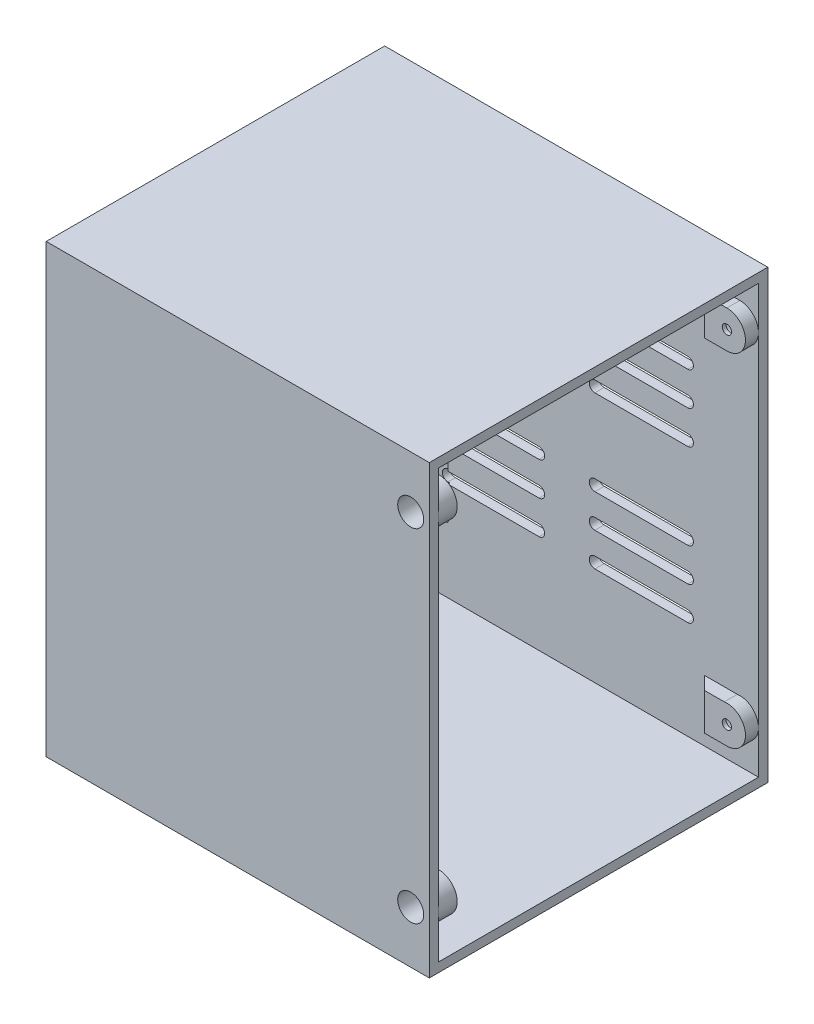
SolidWorks part; units mm, degrees
ref_plane "Front Plane" through (0, 0, 0) normal (0, 0, 1) x (1, 0, 0)
ref_plane "Top Plane" through (0, 0, 0) normal (0, 1, 0) x (1, 0, 0)
ref_plane "Right Plane" through (0, 0, 0) normal (1, 0, 0) x (0, 0, -1)
sketch "Sketch1" plane through (205.5525, 0, 0) normal (1, 0, 0) x (0, 0, -1)
  line L0 (1.5129, 48.8646) -> (1.513, -71.1354) construction
  line L1 (-89.4871, 48.8644) -> (1.5129, 48.8646) construction
  line L2 (-89.4871, 48.8644) -> (-89.487, -71.1356) construction
  line L3 (-89.487, -71.1356) -> (1.513, -71.1354) construction
  line L4 (1.5129, 48.8646) -> (1.513, -71.1354)
  line L5 (-89.4871, 48.8644) -> (1.5129, 48.8646)
  line L6 (-89.4871, 48.8644) -> (-89.487, -71.1356)
  line L7 (-89.487, -71.1356) -> (1.513, -71.1354)
  line L8 (-86.987, -68.6356) -> (-0.987, -68.6355)
  line L9 (-0.9871, 46.3645) -> (-0.987, -68.6355)
  line L10 (-86.9871, 46.3644) -> (-0.9871, 46.3645)
  line L11 (-86.9871, 46.3644) -> (-86.987, -68.6356)
  dimension "D1" = 2.5
extrude "Boss-Extrude1" add sketch "Sketch1" along normal up to surface (103 mm away)
sketch "Sketch2" plane through (0, 0, 86.9871) normal (0, 0, -1) x (-1, 0, 0)
  line L0 (-205.5525, 46.3645) -> (-205.5525, -68.6355) construction
  line L1 (-208.4525, -46.1353) -> (-206.5525, -46.1353)
  line L2 (-208.4525, -46.1353) -> (-208.4525, -40.1355)
  line L3 (-208.4525, -40.1355) -> (-206.5525, -40.1355)
  line L4 (-206.5525, -46.1353) -> (-206.5525, -40.1355)
  line L5 (-206.5525, 23.8645) -> (-208.4525, 23.8645)
  line L6 (-206.5525, 23.8645) -> (-206.5525, 17.8647)
  line L7 (-206.5525, 17.8647) -> (-208.4525, 17.8647)
  line L8 (-208.4525, 23.8645) -> (-208.4525, 17.8647)
  dimension "D1" = 0.1
  dimension "D2" = 1
  dimension "D3" = 0.1
  dimension "D4" = 1
  dimension "D5" = 0
  dimension "D6" = 0
  dimension "D7" = 0
  dimension "D8" = 0
extrude "Boss-Extrude2" add sketch "Sketch2" along normal offset from surface (1.3 mm away) 0.2
sketch "Sketch3" plane through (0, 0, 0.9871) normal (0, 0, 1) x (1, 0, 0)
  line L1 (210.0525, 28.8645) -> (225.0525, 28.8645)
  line L2 (210.0525, 28.8645) -> (210.0525, -51.1355)
  line L3 (210.0525, -51.1355) -> (225.0525, -51.1355)
  line L4 (225.0525, 28.8645) -> (225.0525, -51.1355)
  line L6 (205.5525, -68.6355) -> (205.5525, 46.3645) construction
  line L7 (308.5525, -71.1355) -> (205.5525, -71.1355) construction
  line L8 (308.5525, 48.8645) -> (205.5525, 48.8645) construction
  dimension "D1" = 4.5
  dimension "D2" = 15
  dimension "D3" = 20
  dimension "D4" = 20
extrude "Cut-Extrude1" cut sketch "Sketch3" against normal blind 0.5
sketch "Sketch4" plane through (0, 0, 0.9871) normal (0, 0, 1) x (1, 0, 0)
  line L0 (211.5525, 39.8645) -> (205.5525, 39.8645)
  line L1 (205.5525, -68.6355) -> (205.5525, 46.3645) construction
  line L2 (211.5525, 29.8645) -> (205.5525, 29.8645)
  line L3 (205.5525, 29.8645) -> (205.5525, 39.8645)
  line L4 (211.5525, -52.1355) -> (205.5525, -52.1355)
  line L5 (211.5525, -62.1355) -> (205.5525, -62.1355)
  line L6 (205.5525, -62.1355) -> (205.5525, -52.1355)
  line L7 (303.5525, -62.1355) -> (293.5525, -62.1355)
  line L8 (293.5525, -62.1355) -> (293.5525, -52.1855)
  line L9 (303.6025, -52.1855) -> (293.5525, -52.1855)
  line L10 (303.5525, 29.8645) -> (293.5525, 29.8645)
  line L11 (303.5525, 39.8645) -> (293.5525, 39.8645)
  line L12 (293.5525, 39.8645) -> (293.5525, 29.8645)
  circle A0 centre (211.5525, 34.8645) radius 2.25 construction
  circle A1 centre (211.5525, -57.1355) radius 2.25 construction
  circle A2 centre (211.5525, 34.8645) radius 2.25 construction
  circle A3 centre (211.5525, -57.1355) radius 2.25 construction
  circle A4 centre (211.5525, -57.1355) radius 5
  circle A5 centre (211.5525, 34.8645) radius 5
  circle A6 centre (211.5525, -57.1355) radius 3.5
  circle A7 centre (211.5525, 34.8645) radius 3.5
  circle A8 centre (211.5525, 34.8645) radius 1.25
  circle A9 centre (211.5525, -57.1355) radius 1.25
  circle A10 centre (303.5525, 34.8645) radius 1.6 construction
  circle A11 centre (303.5525, -57.1355) radius 1.6 construction
  circle A12 centre (303.5525, 34.8645) radius 1.6 construction
  circle A13 centre (303.5525, -57.1355) radius 1.6 construction
  circle A14 centre (303.5525, 34.8645) radius 5
  circle A15 centre (303.5525, -57.1355) radius 5
  circle A16 centre (303.5525, -57.1355) radius 3.5
  circle A17 centre (303.5525, -57.1355) radius 1.25
  circle A18 centre (303.5525, 34.8645) radius 3.5
  circle A19 centre (303.5525, 34.8645) radius 1.25
  line M7 (205.5525, 46.3645) -> (205.5525, -68.6355)
  dimension "D1" = 10
  dimension "D2" = 10
  dimension "D3" = 7
  dimension "D4" = 7
  dimension "D5" = 2.5
  dimension "D6" = 2.5
  dimension "D7" = 10
  dimension "D8" = 7
  dimension "D9" = 2.5
  dimension "D10" = 10
  dimension "D11" = 7
  dimension "D12" = 2.5
  dimension "D13" = 10
  dimension "D14" = 10
extrude "Boss-Extrude3" add sketch "Sketch4" along normal up to surface (3.5 mm away) contours A5 A7 | A4 A6 | A5 L0 L2 M7 | A4 L4 L5 M7 | A15 A16 | A14 A18 | A14 L11 L12 L10 | A15 L9 L8 L7 region at (206.4359, 34.8645, 0.9871) region at (208.5525, -52.2521, 0.9871) region at (214.988, 38.3001, 0.9871) region at (214.988, -53.6999, 0.9871) region at (298.7061, -57.479, 0.9871) region at (296.6787, -57.1748, 0.9871) region at (296.6915, 34.8645, 0.9871) region at (298.6939, 34.8645, 0.9871)
extrude "Boss-Extrude4" add sketch "Sketch4<3>" against normal blind 1 from surface contours A7 A8 | A18 A19 | A16 A17 | A6 A9 region at (208.1515, -57.1355, 0.9871) region at (208.1515, 34.8645, 0.9871) region at (300.1515, -57.1355, 0.9871) region at (300.1515, 34.8645, 0.9871) starting at face at (307.0525, 34.8645, 4.4871)
sketch "Sketch4<3>" plane through (0, 0, 0.9871) normal (0, 0, 1) x (1, 0, 0) same geometry as "Sketch4"
extrude "Cut-Extrude2" cut sketch "Sketch4<4>" against normal through all contours A6 A9 | A9 | A7 A8 | A8 | A17 | A16 A17 | A19 | A18 A19 region at (208.1515, -57.1355, 0.9871) region at (208.1515, 34.8645, 0.9871) region at (211.5525, 34.8645, 0.9871) region at (211.5525, -57.1355, 0.9871) region at (300.1515, -57.1355, 0.9871) region at (303.5525, -57.1355, 0.9871) region at (300.1515, 34.8645, 0.9871) region at (303.5525, 34.8645, 0.9871)
sketch "Sketch4<4>" plane through (0, 0, 0.9871) normal (0, 0, 1) x (1, 0, 0) same geometry as "Sketch4"
chamfer "Chamfer1" distance 4 angle 45 1 edges at (293.5525, -57.1605, 4.4871)
chamfer "Chamfer2" distance 4 angle 45 1 edges at (293.5525, 34.8645, 4.4871)
sketch "Sketch5" plane through (0, 0, -1.5129) normal (0, 0, -1) x (-1, 0, 0)
  line L0 (-257.0525, 48.8645) -> (-257.0525, -71.1355) construction
  line L1 (-308.5525, 48.8645) -> (-205.5525, 48.8645) construction
  line L2 (-308.5525, -71.1355) -> (-205.5525, -71.1355) construction
  line L3 (-308.5525, -11.1355) -> (-205.5525, -11.1355) construction
  line L4 (-308.5525, -71.1355) -> (-308.5525, 48.8645) construction
  line L5 (-205.5525, 48.8645) -> (-205.5525, -71.1355) construction
  line L6 (-289.5525, 10.8645) -> (-289.5525, 7.8645)
  line L7 (-289.5525, 1.8645) -> (-264.5525, 1.8645)
  line L8 (-289.5525, 1.8645) -> (-289.5525, -1.1355)
  line L9 (-289.5525, -1.1355) -> (-264.5525, -1.1355)
  line L10 (-264.5525, 1.8645) -> (-264.5525, -1.1355)
  line L11 (-289.5525, 10.8645) -> (-264.5525, 10.8645)
  line L12 (-264.5525, 10.8645) -> (-264.5525, 7.8645)
  line L13 (-289.5525, 7.8645) -> (-264.5525, 7.8645)
  line L14 (-289.5525, 19.8645) -> (-289.5525, 16.8645)
  line L15 (-289.5525, 19.8645) -> (-264.5525, 19.8645)
  line L16 (-264.5525, 19.8645) -> (-264.5525, 16.8645)
  line L17 (-289.5525, 16.8645) -> (-264.5525, 16.8645)
  line L18 (-224.5525, 16.8645) -> (-249.5525, 16.8645)
  line L19 (-249.5525, 19.8645) -> (-249.5525, 16.8645)
  line L20 (-224.5525, 19.8645) -> (-249.5525, 19.8645)
  line L21 (-224.5525, 19.8645) -> (-224.5525, 16.8645)
  line L22 (-224.5525, 7.8645) -> (-249.5525, 7.8645)
  line L23 (-249.5525, 10.8645) -> (-249.5525, 7.8645)
  line L24 (-224.5525, 10.8645) -> (-249.5525, 10.8645)
  line L25 (-249.5525, 1.8645) -> (-249.5525, -1.1355)
  line L26 (-224.5525, -1.1355) -> (-249.5525, -1.1355)
  line L27 (-224.5525, 1.8645) -> (-224.5525, -1.1355)
  line L28 (-224.5525, 1.8645) -> (-249.5525, 1.8645)
  line L29 (-224.5525, 10.8645) -> (-224.5525, 7.8645)
  line L30 (-224.5525, -33.1355) -> (-224.5525, -30.1355)
  line L31 (-224.5525, -24.1355) -> (-249.5525, -24.1355)
  line L32 (-224.5525, -24.1355) -> (-224.5525, -21.1355)
  line L33 (-224.5525, -21.1355) -> (-249.5525, -21.1355)
  line L34 (-249.5525, -24.1355) -> (-249.5525, -21.1355)
  line L35 (-224.5525, -33.1355) -> (-249.5525, -33.1355)
  line L36 (-249.5525, -33.1355) -> (-249.5525, -30.1355)
  line L37 (-224.5525, -30.1355) -> (-249.5525, -30.1355)
  line L38 (-224.5525, -42.1355) -> (-224.5525, -39.1355)
  line L39 (-224.5525, -42.1355) -> (-249.5525, -42.1355)
  line L40 (-249.5525, -42.1355) -> (-249.5525, -39.1355)
  line L41 (-224.5525, -39.1355) -> (-249.5525, -39.1355)
  line L42 (-289.5525, -39.1355) -> (-264.5525, -39.1355)
  line L43 (-264.5525, -42.1355) -> (-264.5525, -39.1355)
  line L44 (-289.5525, -42.1355) -> (-264.5525, -42.1355)
  line L45 (-289.5525, -42.1355) -> (-289.5525, -39.1355)
  line L46 (-289.5525, -30.1355) -> (-264.5525, -30.1355)
  line L47 (-264.5525, -33.1355) -> (-264.5525, -30.1355)
  line L48 (-289.5525, -33.1355) -> (-264.5525, -33.1355)
  line L49 (-264.5525, -24.1355) -> (-264.5525, -21.1355)
  line L50 (-289.5525, -21.1355) -> (-264.5525, -21.1355)
  line L51 (-289.5525, -24.1355) -> (-289.5525, -21.1355)
  line L52 (-289.5525, -24.1355) -> (-264.5525, -24.1355)
  line L53 (-289.5525, -33.1355) -> (-289.5525, -30.1355)
  arc A0 (-264.5525, 1.8645) -> (-264.5525, -1.1355) centre (-264.5525, 0.3645) cw
  arc A1 (-289.5525, -1.1355) -> (-289.5525, 1.8645) centre (-289.5525, 0.3645) cw
  arc A2 (-264.5525, 10.8645) -> (-264.5525, 7.8645) centre (-264.5525, 9.3645) cw
  arc A3 (-289.5525, 7.8645) -> (-289.5525, 10.8645) centre (-289.5525, 9.3645) cw
  arc A4 (-264.5525, 19.8645) -> (-264.5525, 16.8645) centre (-264.5525, 18.3645) cw
  arc A5 (-289.5525, 16.8645) -> (-289.5525, 19.8645) centre (-289.5525, 18.3645) cw
  arc A6 (-224.5525, 16.8645) -> (-224.5525, 19.8645) centre (-224.5525, 18.3645) ccw
  arc A7 (-249.5525, 19.8645) -> (-249.5525, 16.8645) centre (-249.5525, 18.3645) ccw
  arc A8 (-224.5525, 7.8645) -> (-224.5525, 10.8645) centre (-224.5525, 9.3645) ccw
  arc A9 (-249.5525, 10.8645) -> (-249.5525, 7.8645) centre (-249.5525, 9.3645) ccw
  arc A10 (-224.5525, -1.1355) -> (-224.5525, 1.8645) centre (-224.5525, 0.3645) ccw
  arc A11 (-249.5525, 1.8645) -> (-249.5525, -1.1355) centre (-249.5525, 0.3645) ccw
  arc A12 (-249.5525, -24.1355) -> (-249.5525, -21.1355) centre (-249.5525, -22.6355) cw
  arc A13 (-224.5525, -21.1355) -> (-224.5525, -24.1355) centre (-224.5525, -22.6355) cw
  arc A14 (-249.5525, -33.1355) -> (-249.5525, -30.1355) centre (-249.5525, -31.6355) cw
  arc A15 (-224.5525, -30.1355) -> (-224.5525, -33.1355) centre (-224.5525, -31.6355) cw
  arc A16 (-249.5525, -42.1355) -> (-249.5525, -39.1355) centre (-249.5525, -40.6355) cw
  arc A17 (-224.5525, -39.1355) -> (-224.5525, -42.1355) centre (-224.5525, -40.6355) cw
  arc A18 (-289.5525, -39.1355) -> (-289.5525, -42.1355) centre (-289.5525, -40.6355) ccw
  arc A19 (-264.5525, -42.1355) -> (-264.5525, -39.1355) centre (-264.5525, -40.6355) ccw
  arc A20 (-289.5525, -30.1355) -> (-289.5525, -33.1355) centre (-289.5525, -31.6355) ccw
  arc A21 (-264.5525, -33.1355) -> (-264.5525, -30.1355) centre (-264.5525, -31.6355) ccw
  arc A22 (-289.5525, -21.1355) -> (-289.5525, -24.1355) centre (-289.5525, -22.6355) ccw
  arc A23 (-264.5525, -24.1355) -> (-264.5525, -21.1355) centre (-264.5525, -22.6355) ccw
  dimension "D1" = 3
  dimension "D2" = 25
  dimension "D3" = 10
  dimension "D4" = 7.5
  dimension "D6" = 6
  dimension "D5" = 3
extrude "Cut-Extrude3" cut sketch "Sketch5" against normal blind 3 contours L14 L17 L16 L15 | A5 L14 | A4 L16 | A1 L8 | L10 L7 L8 L9 | A0 L10 | A2 L12 | L6 L13 L12 L11 | A3 L6 | A17 L38 | L38 L41 L40 L39 | A16 L40 | A14 L36 | L30 L37 L36 L35 | A15 L30 | A13 L32 | L34 L31 L32 L33 | A12 L34 | L51 A22 | L51 L52 L49 L50 | L49 A23 | L47 A21 | L53 L48 L47 L46 | L53 A20 | L45 A18 | L45 L44 L43 L42 | L43 A19 | L21 A6 | L21 L20 L19 L18 | L19 A7 | L23 A9 | L29 L24 L23 L22 | L29 A8 | L27 A10 | L27 L28 L25 L26 | L25 A11 region at (277.0525, 9.3645, -1.5129) region at (290.1891, 9.3645, -1.5129) region at (263.9159, 9.3645, -1.5129) region at (277.0525, 0.3645, -1.5129) region at (290.1891, 0.3645, -1.5129) region at (263.9159, 0.3645, -1.5129) region at (277.0525, 18.3645, -1.5129) region at (290.1891, 18.3645, -1.5129) region at (263.9159, 18.3645, -1.5129) region at (237.0525, 18.3645, -1.5129) region at (223.9159, 18.3645, -1.5129) region at (250.1891, 18.3645, -1.5129) region at (237.0525, 9.3645, -1.5129) region at (223.9159, 9.3645, -1.5129) region at (250.1891, 9.3645, -1.5129) region at (237.0525, 0.3645, -1.5129) region at (250.1891, 0.3645, -1.5129) region at (223.9159, 0.3645, -1.5129) region at (237.0525, -31.6355, -1.5129) region at (223.9159, -31.6355, -1.5129) region at (250.1891, -31.6355, -1.5129) region at (237.0525, -22.6355, -1.5129) region at (223.9159, -22.6355, -1.5129) region at (250.1891, -22.6355, -1.5129) region at (237.0525, -40.6355, -1.5129) region at (223.9159, -40.6355, -1.5129) region at (250.1891, -40.6355, -1.5129) region at (277.0525, -40.6355, -1.5129) region at (290.1891, -40.6355, -1.5129) region at (263.9159, -40.6355, -1.5129) region at (277.0525, -31.6355, -1.5129) region at (290.1891, -31.6355, -1.5129) region at (263.9159, -31.6355, -1.5129) region at (277.0525, -22.6355, -1.5129) region at (263.9159, -22.6355, -1.5129) region at (290.1891, -22.6355, -1.5129)
extrude "Boss-Extrude5" add sketch "Sketch4<6>" against normal up to surface (5 mm away) from surface contours A15 L9 L8 L7 | A15 A16 | A14 L11 L12 L10 | A14 A18 region at (298.7061, -57.479, 0.9871) region at (296.6787, -57.1748, 0.9871) region at (296.6915, 34.8645, 0.9871) region at (298.6939, 34.8645, 0.9871) starting at face at (257.0525, -11.1355, 86.9871)
sketch "Sketch4<6>" plane through (0, 0, 0.9871) normal (0, 0, 1) x (1, 0, 0) same geometry as "Sketch4"
extrude "Boss-Extrude6" add sketch "Sketch4<7>" along normal blind 1 from surface contours A14 A18 | A18 A19 | A16 A17 | A15 A16 region at (298.7061, -57.479, 0.9871) region at (298.6939, 34.8645, 0.9871) region at (300.1515, -57.1355, 0.9871) region at (300.1515, 34.8645, 0.9871) starting at face at (299.8025, 34.8645, 81.9871)
sketch "Sketch4<7>" plane through (0, 0, 0.9871) normal (0, 0, 1) x (1, 0, 0) same geometry as "Sketch4"
extrude "Cut-Extrude4" cut sketch "Sketch4<8>" along normal through all from surface contours A16 A17 | A18 A19 | A17 | A19 region at (300.1515, -57.1355, 0.9871) region at (303.5525, -57.1355, 0.9871) region at (300.1515, 34.8645, 0.9871) region at (303.5525, 34.8645, 0.9871) starting at face at (207.5025, 20.8646, 86.9871)
sketch "Sketch4<8>" plane through (0, 0, 0.9871) normal (0, 0, 1) x (1, 0, 0) same geometry as "Sketch4"
chamfer "Chamfer3" distance 5 angle 45 1 edges at (293.5525, -57.1605, 81.9871)
chamfer "Chamfer4" distance 5 angle 45 1 edges at (293.5525, 34.8645, 81.9871)
equation "\"R\"=9.03994"
equation "\"R_MOUNT_OUTER\"=10"
equation "\"D1@Sketch4\"=\"R_MOUNT_OUTER\""
equation "\"D2@Sketch4\"=\"R_MOUNT_OUTER\""
equation "\"R_MOUNT_INNER\"=7"
equation "\"D3@Sketch4\"=\"R_MOUNT_INNER\""
equation "\"D4@Sketch4\"=\"R_MOUNT_INNER\""
equation "\"R_SCREW\"=2.5"
equation "\"D5@Sketch4\"=\"R_SCREW\""
equation "\"D6@Sketch4\"=\"R_SCREW\""
equation "\"D7@Sketch4\"=\"R_MOUNT_OUTER\""
equation "\"D8@Sketch4\"=\"R_MOUNT_INNER\""
equation "\"D9@Sketch4\"=\"R_SCREW\""
equation "\"D10@Sketch4\"=\"R_MOUNT_OUTER\""
equation "\"D11@Sketch4\"=\"R_MOUNT_INNER\""
equation "\"D12@Sketch4\"=\"R_SCREW\""
